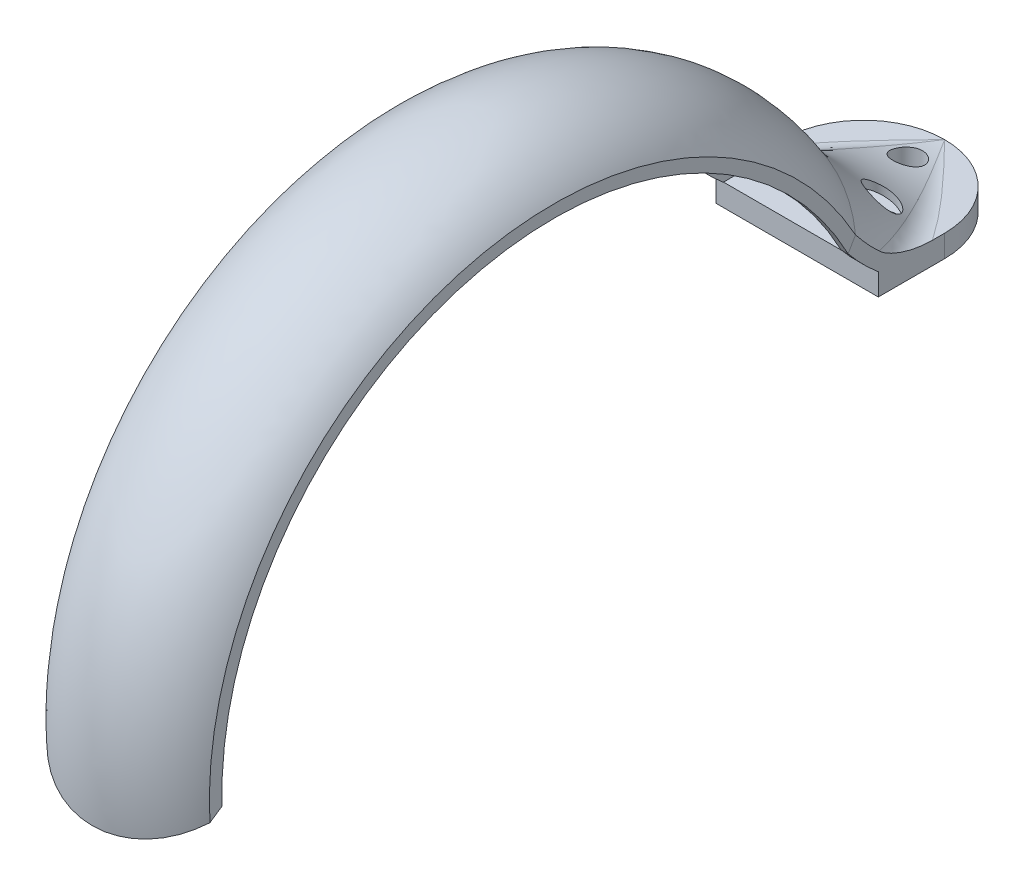
SolidWorks part; units mm, degrees
material "ABS"
ref_plane "Front Plane" through (0, 0, 0) normal (0, 0, 1) x (1, 0, 0)
ref_plane "Top Plane" through (0, 0, 0) normal (0, 1, 0) x (1, 0, 0)
ref_plane "Right Plane" through (0, 0, 0) normal (1, 0, 0) x (0, 0, -1)
sketch "Sketch2" plane through (0, 0, 0) normal (0, 1, 0) x (1, 0, 0)
  line L0 (-27.5, 0) -> (-27.5, -22.5)
  line L1 (-27.5, -22.5) -> (27.5, -22.5)
  line L2 (27.5, -22.5) -> (27.5, 0)
  line L3 (-13.75, -7.5) -> (13.75, -7.5) construction
  arc A0 (27.5, 0) -> (-27.5, 0) centre (0, 0) ccw
  circle A1 centre (13.75, -7.5) radius 5
  circle A2 centre (-13.75, -7.5) radius 5
  circle A3 centre (0, 15) radius 5
  point P1 (0, 27.5)
  point P13 (0, -7.5)
  dimension "D6" = 10
  dimension "D1" = 55
  dimension "D2" = 50
  dimension "D3" = 12.5
  dimension "D4" = 35
  dimension "D5" = 27.5
extrude "Boss-Extrude1" add sketch "Sketch2" along normal blind 7.5
sketch "Sketch3" plane through (0, 0, 0) normal (1, 0, 0) x (0, 0, -1)
  line L0 (-22.5, 7.5) -> (0, 7.5) construction
  line L1 (-347.457, -49.5) -> (92.6839, -49.5) construction
  line L2 (27.5, 7.5) -> (27.5, 35.1161) construction
  line L3 (27.5, 35.1161) -> (-22.7111, 35.1161) construction
  arc A0 (-22.7111, 35.1161) -> (27.5, 7.5) centre (27.5, 66.9545) ccw
  arc A1 (-22.7111, 35.1161) -> (-261.6317, -49.5) centre (-132.5, -34.5) ccw
  dimension "D1" = 260
  dimension "D2" = 110
  dimension "D3" = 42
  dimension "D4" = 15
ref_plane "Plane1" through (0, 7.5, -27.5) normal (0, 0, -1) x (-1, 0, 0)
sketch "Sketch5" plane through (0, 7.5, 0) normal (0, 0, -1) x (-1, 0, 0)
  line L0 (-27.5, -13.2578) -> (-27.5, -8.2578)
  line L1 (-27.5, 0) -> (-27.5, -7.5) construction
  line L2 (27.5, -13.2578) -> (27.5, -8.2578)
  line L3 (27.5, 0) -> (27.5, -7.5) construction
  line L4 (-82.3164, 6.7422) -> (50.4916, 6.7422) construction
  line L5 (-25, -13.2578) -> (-25, -9.009)
  line L6 (25, -13.2578) -> (25, -9.009)
  line L7 (-27.5, -13.2578) -> (-25, -13.2578)
  line L8 (27.5, -13.2578) -> (25, -13.2578)
  arc A0 (27.5, -8.2578) -> (-27.5, -8.2578) centre (0, -25.9661) ccw
  arc A1 (25, -9.009) -> (-25, -9.009) centre (0, -25.9661) ccw
  point P21 (0, 6.7422)
  dimension "D1" = 5
  dimension "D3" = 2.5
  dimension "D2" = 15
sweep "Sweep1" add profiles "Sketch5" path "Sketch3"
fillet "Fillet1" radius 10 2 edges at (-17.7138, 7.5, -3.4871) (17.7138, 7.5, -3.4871)
sketch "Sketch7" plane through (0, 0, 0) normal (0, 1, 0) x (1, 0, 0)
  line L0 (-27.5, 0) -> (-27.5, 36.7508)
  line L1 (-27.5, 36.7508) -> (27.5, 36.7508)
  line L2 (27.5, 36.7508) -> (27.5, 0)
  circle A0 centre (0, 0) radius 27.5
extrude "Cut-Extrude1" cut sketch "Sketch7" against normal through all both and the other way through all contours A0 L2 L1 L0 region at (0, 0, -27.9314)
sketch "Sketch8" plane through (0, 0, 0) normal (1, 0, 0) x (0, 0, -1)
  line L0 (27.5, 3.375) -> (27.5, 11.625) construction
  line L1 (27.5, -9.1108) -> (-22.5, -9.1108)
  line L2 (27.5, -9.1108) -> (27.5, 0)
  line L3 (27.5, 0) -> (-22.5, 0)
  line L4 (-22.5, -9.1108) -> (-22.5, 0)
extrude "Cut-Extrude2" cut sketch "Sketch8" against normal through all both and the other way through all
extrude "Cut-Extrude3" cut sketch "Sketch2<2>" along normal through all both contours A3 | A1 | A2 region at (13.75, 0, 7.5) region at (-13.75, 0, 7.5) region at (0, 0, -15)
sketch "Sketch2<2>" plane through (0, 0, 0) normal (0, 1, 0) x (1, 0, 0) same geometry as "Sketch2"
